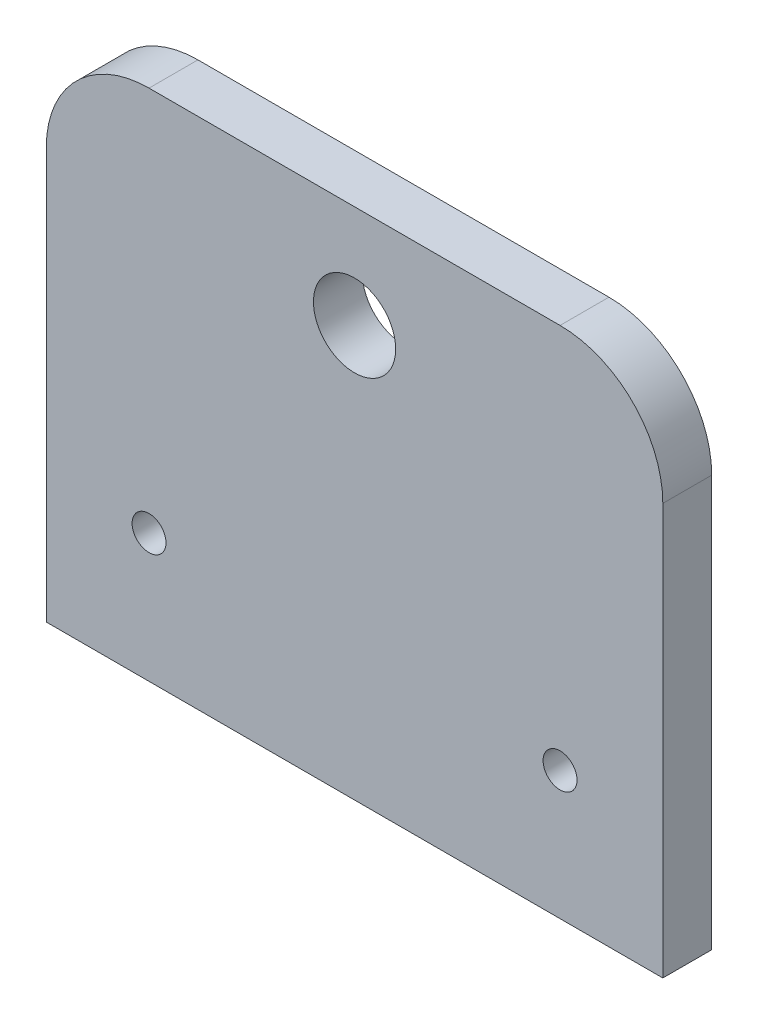
SolidWorks part; units mm, degrees
ref_plane "Front Plane" through (0, 0, 0) normal (0, 0, 1) x (1, 0, 0)
ref_plane "Top Plane" through (0, 0, 0) normal (0, 1, 0) x (1, 0, 0)
ref_plane "Right Plane" through (0, 0, 0) normal (1, 0, 0) x (0, 0, -1)
sketch "Sketch1" plane through (0, 0, 0) normal (0, 0, 1) x (1, 0, 0)
  line L1 (0, 0) -> (60, 0)
  line L2 (0, 0) -> (0, 50)
  line L3 (0, 50) -> (60, 50)
  line L4 (60, 0) -> (60, 50)
  dimension "D1" = 50
  dimension "D2" = 60
extrude "Boss-Extrude1" add sketch "Sketch1" along normal blind 4.76
sketch "Sketch2" plane through (0, 0, 4.76) normal (0, 0, 1) x (1, 0, 0)
  line L0 (0, 12.5) -> (60, 12.5) construction
  line L1 (0, 50) -> (0, 0) construction
  line L2 (60, 0) -> (60, 50) construction
  line L3 (0, 0) -> (60, 0) construction
  line L4 (30, 50) -> (30, 0) construction
  line L5 (60, 50) -> (0, 50) construction
  circle A0 centre (10, 12.5) radius 1.65
  circle A2 centre (50, 12.5) radius 1.65
  circle A3 centre (30, 40) radius 4
  dimension "D2" = 3.3
  dimension "D4" = 8
  dimension "D1" = 12.5
  dimension "D3" = 20
  dimension "D5" = 10
extrude "Cut-Extrude1" cut sketch "Sketch2" against normal through all
fillet "Fillet1" radius 10 2 edges at (60, 50, 2.38) (0, 50, 2.38)
equation "\"Screw Size\"= 8"
equation "\"D4@Sketch2\"= \"Screw Size\""
